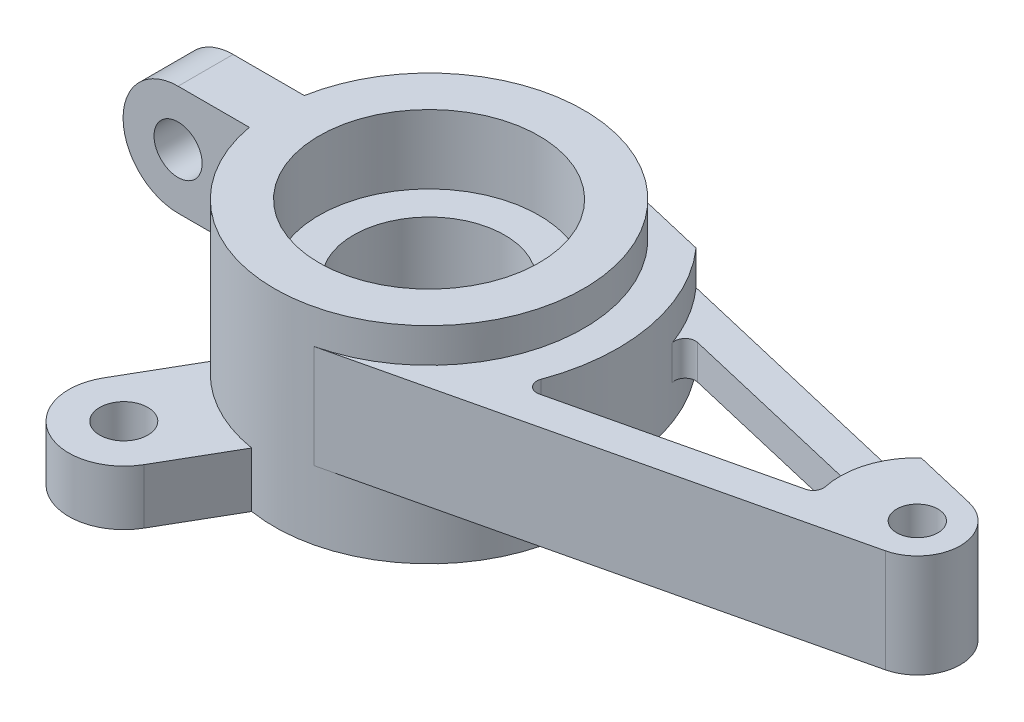
SolidWorks part; units mm, degrees
material "AISI Type 316L stainless steel"
ref_plane "Front Plane" through (0, 0, 0) normal (0, 0, 1) x (1, 0, 0)
ref_plane "Top Plane" through (0, 0, 0) normal (0, 1, 0) x (1, 0, 0)
ref_plane "Right Plane" through (0, 0, 0) normal (1, 0, 0) x (0, 0, -1)
sketch "Sketch1" plane through (0, 0, 0) normal (0, 1, 0) x (1, 0, 0)
  circle A0 centre (0, 0) radius 4.5
  dimension "D1" = 9
extrude "Boss-Extrude1" add sketch "Sketch1" along normal blind 6
sketch "Sketch2" plane through (0, 0, 0) normal (0, -1, 0) x (1, 0, 0)
  line L0 (0, 0) -> (0, 5.4402) construction
  line L1 (0, 5.4402) -> (0, 0) construction
  line L2 (0, 0) -> (-7.8572, 0) construction
  line L3 (0, 0) -> (-3.25, 5.6292) construction
  line L4 (-4.6356, 4.8292) -> (-3.4886, 2.8425)
  line L5 (-1.8644, 6.4292) -> (-0.7173, 4.4425)
  line L6 (-1.8644, -6.4292) -> (-0.7173, -4.4425)
  line L7 (-4.6356, -4.8292) -> (-3.4886, -2.8425)
  circle A0 centre (-3.25, 5.6292) radius 1.6
  circle A1 centre (-3.25, 5.6292) radius 0.7
  circle A2 centre (0, 0) radius 4.5 construction
  circle A3 centre (0, 0) radius 4.5
  circle A4 centre (-3.25, -5.6292) radius 0.7
  circle A5 centre (-3.25, -5.6292) radius 1.6
  circle M1 centre (0, 0) radius 4.5
  dimension "D1" = 3.2
  dimension "D2" = 1.4
  dimension "D3" = 30
  dimension "D4" = 6.5
extrude "Boss-Extrude2" add sketch "Sketch2" against normal blind 1.6 contours L7 A5 L6 M1 | A5 A4 | A0 A1 | A0 L4 L5 M1 region at (-2.4474, 0, 4.2389) region at (-4.0274, 0, 6.9756) region at (-2.4474, 0, -4.2389) region at (-2.8476, 0, -4.1274)
sketch "Sketch3" plane through (0, 0, 0) normal (0, 0, 1) x (1, 0, 0)
  line L0 (-3.5, 6) -> (-6.5, 6)
  line L1 (4.5, 6) -> (-4.5, 6) construction
  line L2 (-6.5, 2.8) -> (-3.5, 2.8)
  line L3 (-3.5, 2.8) -> (-3.5, 6)
  arc A0 (-6.5, 6) -> (-6.5, 2.8) centre (-6.5, 4.4) ccw
  circle A1 centre (-6.5, 4.4) radius 0.7
  dimension "D1" = 6.5
  dimension "D2" = 1.6
  dimension "D3" = 1.4
  dimension "D4" = 3
extrude "Boss-Extrude3" add sketch "Sketch3" along normal mid plane 1.6
sketch "Sketch4" plane through (0, 6, 0) normal (0, 1, 0) x (1, 0, 0)
  line L0 (0, 0) -> (14.2, 0) construction
  line L1 (1.0299, 4.3806) -> (14.4861, 1.2168)
  line L2 (1.0299, -4.3806) -> (14.4861, -1.2168)
  line L3 (4.9311, -2.4361) -> (12.0805, -0.7551)
  line L5 (4.9311, 2.4361) -> (12.0805, 0.7551)
  arc A0 (14.4861, -1.2168) -> (14.4861, 1.2168) centre (14.2, 0) ccw
  circle A1 centre (14.2, 0) radius 0.6
  arc A2 (12.6649, 1.645) -> (12.6649, -1.645) centre (14.2, 0) ccw
  arc A3 (-4.4283, -0.8) -> (-4.4283, 0.8) centre (0, 0) ccw construction
  arc A4 (-4.4283, -0.8) -> (-4.4283, 0.8) centre (0, 0) ccw
  arc A5 (4.9311, -2.4361) -> (4.1083, 3.6568) centre (0, 0) ccw
  point P2 (-17.5444, 4.6487)
  arc M2 (-4.4283, -0.8) -> (-4.4283, 0.8) centre (0, 0) ccw
  dimension "D1" = 14.2
  dimension "D2" = 4.5
  dimension "D3" = 2.5
  dimension "D4" = 1.2
  dimension "D5" = 11
extrude "Boss-Extrude4" add sketch "Sketch4" against normal blind 3 from offset 1 contours L0 L2 A2 L3 A5 M2 | A5 L5 A2 L1 | A4 L0 A5 L1 | L1 A2 A1 L2 A0 region at (4.2839, 6, -2.126) region at (6.9339, 6, 2.1341) region at (12.0302, 6, -0.375) region at (8.446, 6, -2.1387) offset against normal yes
extrude "Cut-Extrude1" cut sketch "Sketch4<3>" against normal blind 1 from offset 1 contours A5 L5 A2 L1 region at (8.446, 6, -2.1387) offset against normal yes
sketch "Sketch4<3>" plane through (0, 6, 0) normal (0, 1, 0) x (1, 0, 0) same geometry as "Sketch4"
extrude "Cut-Extrude2" cut sketch "Sketch4<4>" against normal blind 1 from offset 3 contours A5 L5 A2 L1 region at (8.446, 6, -2.1387) offset against normal yes
sketch "Sketch4<4>" plane through (0, 6, 0) normal (0, 1, 0) x (1, 0, 0) same geometry as "Sketch4"
fillet "Fillet1" radius 0.3 4 edges at (12.0805, 3.5, -0.7551) (12.0805, 3.5, 0.7551) (4.9311, 3.5, -2.4361) (4.9311, 3.5, 2.4361)
sketch "Sketch5" plane through (0, 6, 0) normal (0, 1, 0) x (1, 0, 0)
  circle A0 centre (0, 0) radius 3.2
  circle A1 centre (0, 0) radius 2.2
  dimension "D1" = 6.4
  dimension "D2" = 4.4
extrude "Cut-Extrude4" cut sketch "Sketch5" against normal through all contours A1 region at (0, 6, 0)
sketch "Sketch9" plane through (0, 6, 0) normal (0, 1, 0) x (1, 0, 0)
  circle A0 centre (0, 0) radius 3.2
  circle M2 centre (0, 0) radius 2.2
  dimension "D1" = 6.4
extrude "Cut-Extrude5" cut sketch "Sketch9" against normal blind 2 contours A0 M2 region at (-3.1095, 6, 0)
